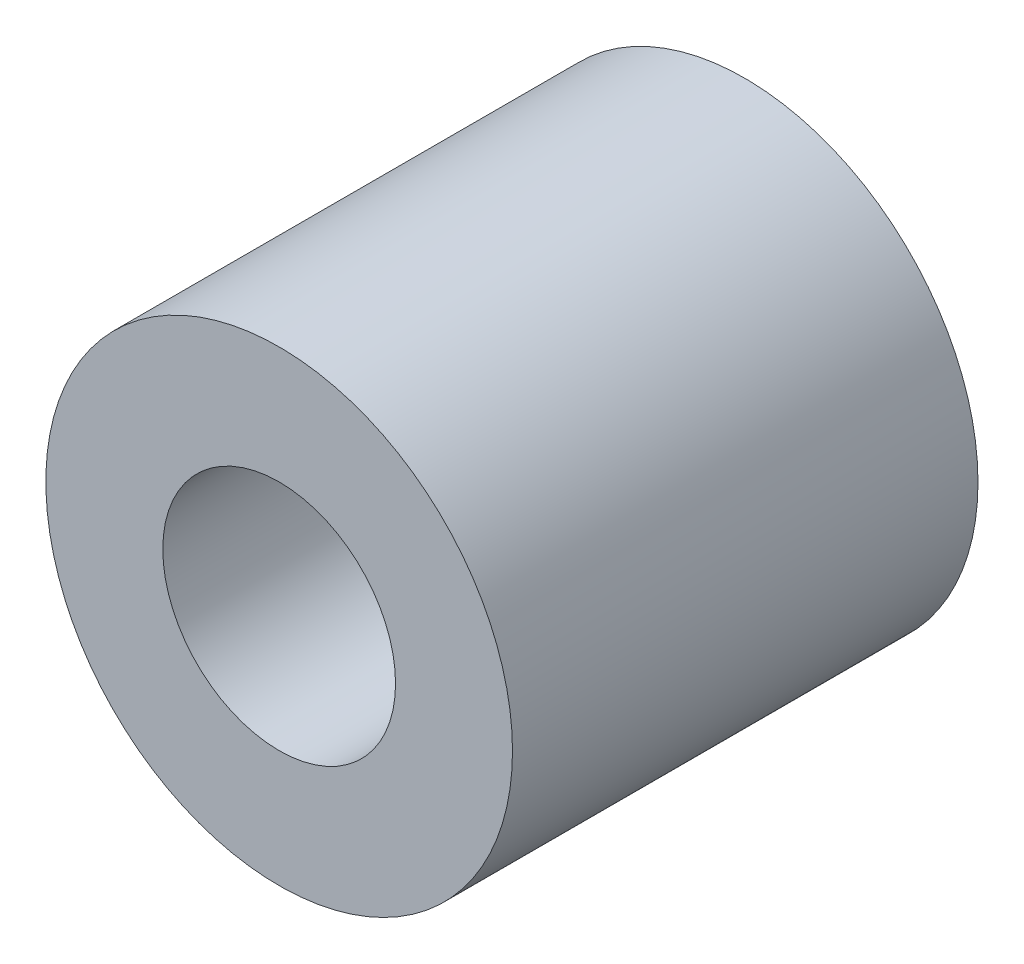
SolidWorks part; units mm, degrees
material "Brass"
ref_plane "Front Plane" through (0, 0, 0) normal (0, 0, 1) x (1, 0, 0)
ref_plane "Top Plane" through (0, 0, 0) normal (0, 1, 0) x (1, 0, 0)
ref_plane "Right Plane" through (0, 0, 0) normal (1, 0, 0) x (0, 0, -1)
sketch "Sketch1" plane through (0, 0, 0) normal (0, 0, 1) x (1, 0, 0)
  circle A0 centre (0, 0) radius 4.01
  circle A1 centre (0, 0) radius 2
  dimension "ID" = 4
  dimension "OD" = 8.02
extrude "Boss-Extrude1" add sketch "Sketch1" along normal mid plane 8
sketch "Sketch2" plane through (0, 0, 0) normal (1, 0, 0) x (0, 0, -1)
  line L0 (-4, 4.01) -> (4, 4.01)
  line L1 (-4, 0) -> (4, 0) construction
  line L2 (-4, 4.01) -> (-4, -4.01) construction
  line L3 (4, -4.01) -> (4, 4.01) construction
  dimension "D1" = 8.02
  dimension "D2" = 8
ref_axis "Center Axis 1" through (0, 0, 4.4) along (0, 0, -1)
ref_plane "Contact Plane 1" through (0, 0, 4) normal (0, 0, 1) x (1, 0, 0)
ref_plane "Contact Plane 2" through (0, 0, -4) normal (0, 0, -1) x (-1, 0, 0)
equation "\"D1@Sketch2\"=\"OD@Sketch1\""
